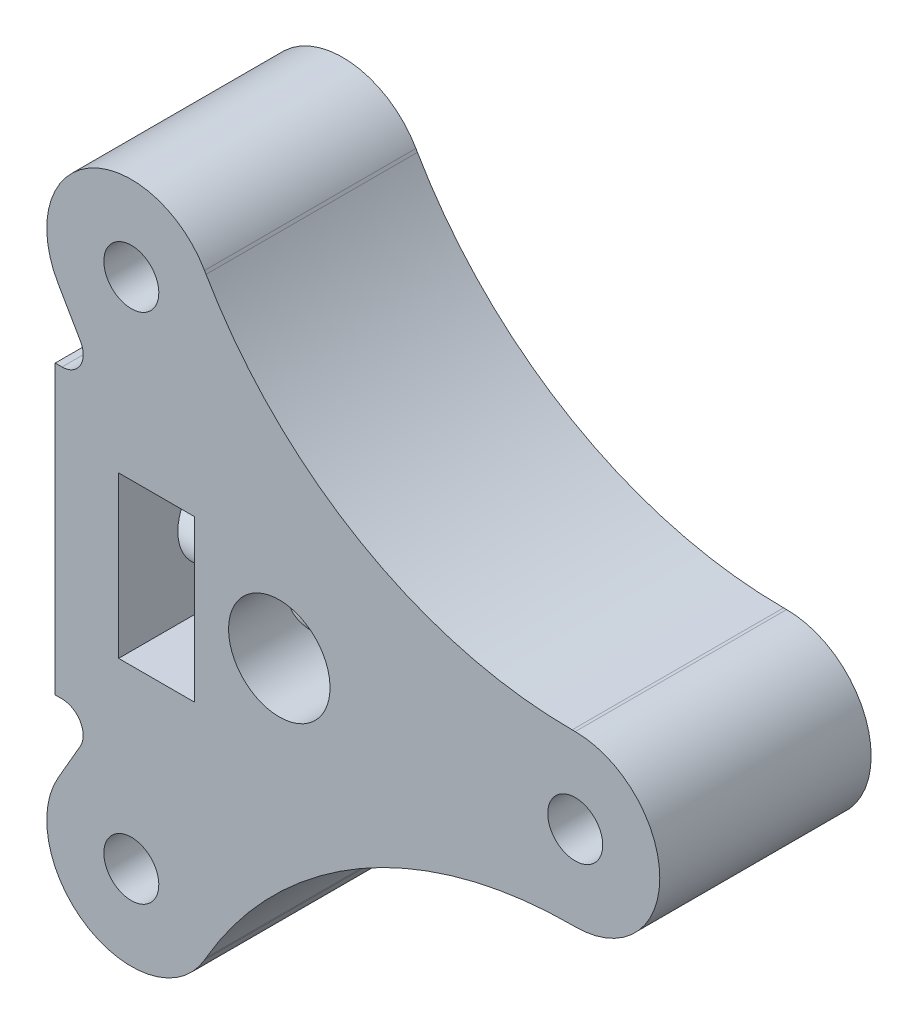
SolidWorks part; units mm, degrees
ref_plane "Front Plane" through (0, 0, 0) normal (0, 0, 1) x (1, 0, 0)
ref_plane "Top Plane" through (0, 0, 0) normal (0, 1, 0) x (1, 0, 0)
ref_plane "Right Plane" through (0, 0, 0) normal (1, 0, 0) x (0, 0, -1)
sketch "Sketch1" plane through (0, 0, 0) normal (0, 0, 1) x (1, 0, 0)
  line L0 (-13.462, 8.636) -> (-1.27, 8.636)
  line L1 (-9.652, 4.826) -> (-5.08, 4.826)
  line L2 (-9.652, 4.826) -> (-9.652, -4.826)
  line L3 (-9.652, -4.826) -> (-5.08, -4.826)
  line L4 (-5.08, 4.826) -> (-5.08, -4.826)
  line L6 (-13.462, -8.636) -> (-1.27, -8.636)
  line L7 (-13.462, 8.636) -> (-13.462, -8.636)
  line L8 (-1.27, 8.636) -> (3.7294, 4.3304)
  line L9 (-1.27, -8.636) -> (3.7294, -4.3304)
  line L10 (-1.27, 8.636) -> (-1.27, -8.636) construction
  circle A0 centre (0, 0) radius 3.048
  arc A1 (3.7294, -4.3304) -> (3.7294, 4.3304) centre (0, 0) ccw
  dimension "D1" = 6.096
  dimension "D2" = 11.43
  dimension "D6" = 5.08
  dimension "D3" = 9.652
  dimension "D4" = 4.572
  dimension "D5" = 4.826
  dimension "D7" = 3.81
extrude "Boss-Extrude1" add sketch "Sketch1" along normal blind 17.78
sketch "Sketch4" plane through (0, 0, 0) normal (0, 0, -1) x (-1, 0, 0)
  circle A0 centre (0, 0) radius 28.575 construction
  dimension "D1" = 57.15
sketch "Sketch3" plane through (-5.08, 0, 0) normal (-1, 0, 0) x (0, 0, 1)
  line L0 (17.78, 4.826) -> (0, 4.826) construction
  line L1 (3.937, -4.826) -> (13.843, -4.826)
  line L2 (3.937, -4.826) -> (3.937, 4.826)
  line L3 (3.937, 4.826) -> (13.843, 4.826)
  line L4 (13.843, -4.826) -> (13.843, 4.826)
  line L5 (3.937, -4.826) -> (13.843, 4.826) construction
  line L6 (3.937, 4.826) -> (13.843, -4.826) construction
  line L8 (3.937, 4.826) -> (0, 4.826)
  line L9 (3.937, 4.826) -> (3.937, -4.826)
  line L10 (3.937, -4.826) -> (0, -4.826)
  line L11 (0, 4.826) -> (0, -4.826)
  point P0 (8.89, 0)
  line M4 (0, 4.826) -> (0, -4.826)
  line M5 (0, -4.826) -> (17.78, -4.826)
  line M7 (17.78, 4.826) -> (0, 4.826)
  dimension "D1" = 9.906
extrude "Boss-Extrude2" add sketch "Sketch3" along normal up to surface (4.572 mm away) contours L2 M5 M7 M4 region at (-5.08, 0, 1.9685) up to face at (-9.652, 0, 8.89)
sketch "Sketch5" plane through (0, 0, 0) normal (0, 0, -1) x (-1, 0, 0)
  line L0 (0, 0) -> (8.89, 15.3979) construction
  line L1 (-2.9329, 5.08) -> (4.4906, 17.9379)
  line L2 (8.6522, 4.826) -> (13.2894, 12.8579)
  line L3 (-2.9329, -5.08) -> (4.4906, -17.9379)
  line L4 (8.6522, -4.826) -> (13.2894, -12.8579)
  line L5 (0, 0) -> (8.89, -15.3979) construction
  line L6 (-2.9329, 5.08) -> (-17.78, 5.08)
  line L7 (-2.9329, -5.08) -> (-17.78, -5.08)
  line L8 (0, 0) -> (-17.78, 0) construction
  line L9 (0, 0) -> (-28.575, 0) construction
  line L11 (8.6522, 4.826) -> (5.08, 4.826)
  line L13 (8.6522, -4.826) -> (5.08, -4.826)
  line L14 (5.08, 4.826) -> (5.08, -4.826)
  arc A1 (13.2894, 12.8579) -> (4.4906, 17.9379) centre (8.89, 15.3979) ccw
  circle A2 centre (8.89, 15.3979) radius 1.651
  arc A4 (4.4906, -17.9379) -> (13.2894, -12.8579) centre (8.89, -15.3979) ccw
  circle A5 centre (8.89, -15.3979) radius 1.651
  arc A7 (-17.78, 5.08) -> (-17.78, -5.08) centre (-17.78, 0) ccw
  circle A8 centre (-17.78, 0) radius 1.651
  circle A9 centre (0, 0) radius 28.575 construction
  circle A12 centre (0, 0) radius 3.048
  point P3 (4.445, 7.699)
  point P13 (4.445, -7.699)
  point P21 (-8.89, 0)
  point P28 (0, 0)
  dimension "D2" = 5.08
  dimension "D3" = 3.302
  dimension "D1" = 17.78
  dimension "D5" = 0
  dimension "D4" = 3
extrude "Boss-Extrude3" add sketch "Sketch5" against normal blind 17.78
fillet "Fillet1" radius 25.4 2 edges at (2.9329, -5.08, 8.89) (2.9329, 5.08, 8.89)
fillet "Fillet2" radius 1.27 2 edges at (-10.8519, 8.636, 8.89) (-10.8519, -8.636, 8.89)
sketch "Sketch2" plane through (-13.462, 0, 0) normal (-1, 0, 0) x (0, 0, 1)
  line L0 (0, 0) -> (17.78, 0) construction
  line L1 (0, 8.636) -> (0, -8.636) construction
  line L2 (17.78, 8.636) -> (17.78, -8.636) construction
  circle A0 centre (8.89, 0) radius 2.794
  dimension "D1" = 5.588
extrude "Cut-Extrude2" cut sketch "Sketch2" against normal blind 12.7
sketch "Sketch7" plane through (-13.462, 0, 0) normal (-1, 0, 0) x (0, 0, 1)
  line L1 (2.54, -25.4) -> (15.24, -25.4)
  line L2 (2.54, -25.4) -> (2.54, 25.4)
  line L3 (2.54, 25.4) -> (15.24, 25.4)
  line L4 (15.24, -25.4) -> (15.24, 25.4)
  line L5 (2.54, -25.4) -> (15.24, 25.4) construction
  line L6 (2.54, 25.4) -> (15.24, -25.4) construction
  line L7 (-3.1594, -31.9325) -> (20.9394, -31.9325)
  line L8 (-3.1594, -31.9325) -> (-3.1594, 31.9325)
  line L9 (-3.1594, 31.9325) -> (20.9394, 31.9325)
  line L10 (20.9394, -31.9325) -> (20.9394, 31.9325)
  line L11 (-3.1594, -31.9325) -> (20.9394, 31.9325) construction
  line L12 (-3.1594, 31.9325) -> (20.9394, -31.9325) construction
  point P0 (8.89, 0)
  point P6 (8.89, 0)
  dimension "D1" = 12.7
  dimension "D2" = 50.8
extrude "Cut-Extrude3" cut sketch "Sketch7" against normal through all both and the other way through all
